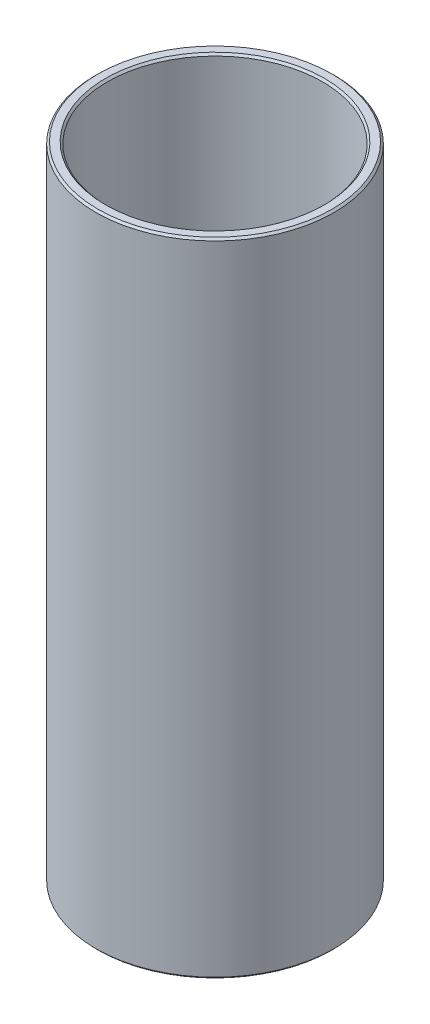
SolidWorks part; units mm, degrees
ref_plane "Front Plane" through (0, 0, 0) normal (0, 0, 1) x (1, 0, 0)
ref_plane "Top Plane" through (0, 0, 0) normal (0, 1, 0) x (1, 0, 0)
ref_plane "Right Plane" through (0, 0, 0) normal (1, 0, 0) x (0, 0, -1)
sketch "Sketch1" plane through (0, 0, 0) normal (0, 1, 0) x (1, 0, 0)
  circle A0 centre (0, 0) radius 50
  dimension "SLEEVE_OD" = 100
extrude "Boss-Extrude1" add sketch "Sketch1" along normal blind 269.3248
sketch "Sketch2" plane through (0, 0, 0) normal (0, 1, 0) x (1, 0, 0)
  circle A0 centre (0, 0) radius 45.1884
  dimension "BORE_D" = 90.3767
extrude "Cut-Extrude1" cut sketch "Sketch2" along normal through all
chamfer "Chamfer1" distance 0.7981 angle 46.642 4 edges at (0, 269.3248, 45.1884) (0, 0, 45.1884) (0, 0, 50) (0, 269.3248, 50) first distance on face at (0, 269.3248, 45.1884) first distance on face at (0, 0, 45.1884) first distance on face at (0, 269.3248, 50)
